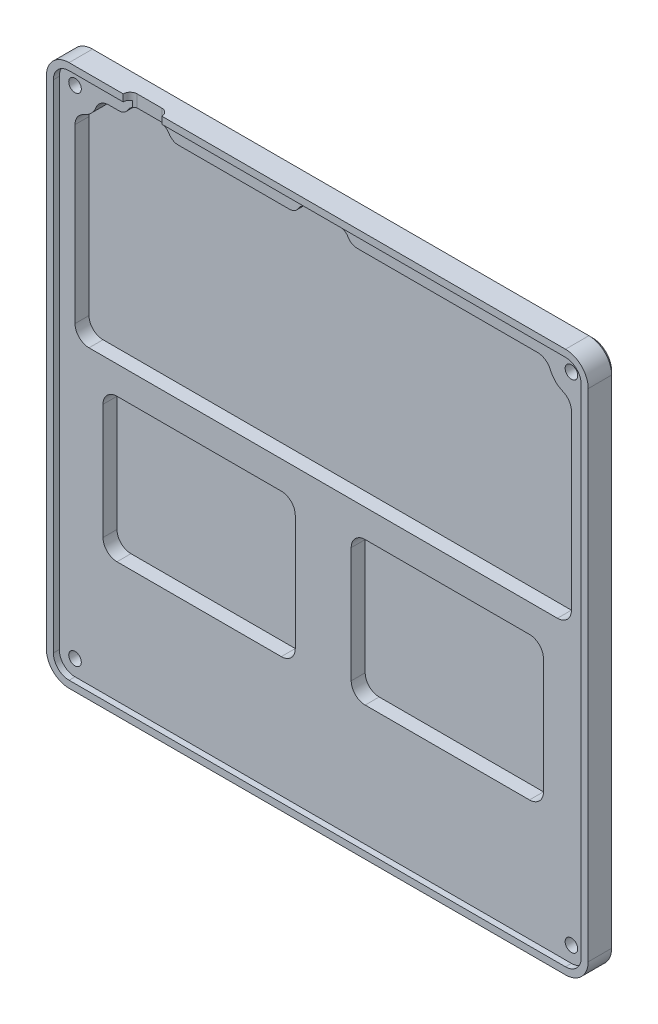
SolidWorks part; units mm, degrees
ref_plane "Front Plane" through (0, 0, 0) normal (0, 0, 1) x (1, 0, 0)
ref_plane "Top Plane" through (0, 0, 0) normal (0, 1, 0) x (1, 0, 0)
ref_plane "Right Plane" through (0, 0, 0) normal (1, 0, 0) x (0, 0, -1)
sketch "Sketch2" plane through (0, 0, 21.1137) normal (0, 0, -1) x (-1, 0, 0)
  line L0 (-26.4015, -76.7464) -> (-26.4015, 65.2536)
  line L1 (-25.9015, -80.7464) -> (124.0985, -80.7464) construction
  line L2 (-25.9015, -80.7464) -> (-25.9015, 69.2536) construction
  line L3 (-25.9015, 69.2536) -> (124.0985, 69.2536) construction
  line L4 (124.0985, -80.7464) -> (124.0985, 69.2536) construction
  line L5 (-21.9015, 69.7536) -> (120.0985, 69.7536)
  line L6 (124.5985, -76.7464) -> (124.5985, 65.2536)
  line L7 (-21.9015, -81.2464) -> (120.0985, -81.2464)
  line L8 (-28.4015, -76.7464) -> (-28.4015, 65.2536)
  line L9 (-21.9015, 71.7536) -> (120.0985, 71.7536)
  line L10 (126.5985, -76.7464) -> (126.5985, 65.2536)
  line L11 (-21.9015, -83.2464) -> (120.0985, -83.2464)
  line L15 (-26.4015, -81.2464) -> (-26.4015, 69.7536) construction
  line L16 (-26.4015, -81.2464) -> (124.5985, -81.2464) construction
  line L17 (-26.4015, 69.7536) -> (124.5985, 69.7536) construction
  line L18 (124.5985, -81.2464) -> (124.5985, 69.7536) construction
  line L19 (-28.4015, 71.7536) -> (126.5985, 71.7536) construction
  line L20 (126.5985, -83.2464) -> (126.5985, 71.7536) construction
  line L21 (-28.4015, -83.2464) -> (126.5985, -83.2464) construction
  line L22 (-28.4015, -83.2464) -> (-28.4015, 71.7536) construction
  line L23 (-21.9015, -80.7464) -> (120.0985, -80.7464) construction
  line L24 (124.0985, -76.7464) -> (124.0985, 65.2536) construction
  line L25 (120.0985, 69.2536) -> (-21.9015, 69.2536) construction
  arc A0 (-26.4015, -76.7464) -> (-21.9015, -81.2464) centre (-21.9015, -76.7464) ccw
  arc A1 (-26.4015, 65.2536) -> (-21.9015, 69.7536) centre (-21.9015, 65.2536) cw
  arc A2 (120.0985, 69.7536) -> (124.5985, 65.2536) centre (120.0985, 65.2536) cw
  arc A3 (124.5985, -76.7464) -> (120.0985, -81.2464) centre (120.0985, -76.7464) cw
  arc A4 (120.0985, 71.7536) -> (126.5985, 65.2536) centre (120.0985, 65.2536) cw
  arc A5 (126.5985, -76.7464) -> (120.0985, -83.2464) centre (120.0985, -76.7464) cw
  arc A6 (-28.4015, -76.7464) -> (-21.9015, -83.2464) centre (-21.9015, -76.7464) ccw
  arc A7 (-28.4015, 65.2536) -> (-21.9015, 71.7536) centre (-21.9015, 65.2536) cw
  dimension "D3" = 4.5
  dimension "D4" = 4.5
  dimension "D5" = 6.5
  dimension "D1" = 0.5
  dimension "D2" = 2
extrude "Boss-Extrude1" add sketch "Sketch2" against normal blind 1.7
sketch "Sketch4" plane through (0, 0, 21.1137) normal (0, 0, -1) x (-1, 0, 0)
  line L0 (-15.4015, 65.2536) -> (41.5985, 65.2536)
  line L4 (-28.4015, -76.7464) -> (-28.4015, 65.2536)
  line L6 (112.0985, -46.7464) -> (112.0985, -5.7464)
  line L8 (126.5985, -76.7464) -> (126.5985, 65.2536)
  line L11 (-21.9015, -83.2464) -> (120.0985, -83.2464)
  line L15 (112.0985, -46.7464) -> (57.0985, -46.7464)
  line L20 (41.0985, -46.7464) -> (41.0985, -5.7464)
  line L21 (120.0985, 2.2536) -> (-21.9015, 2.2536)
  line L23 (41.0985, -5.7464) -> (-13.9015, -5.7464)
  line L26 (41.5985, 68.2536) -> (56.5985, 68.2536)
  line L27 (56.5985, 68.2536) -> (56.5985, 65.2536)
  line L28 (56.5985, 65.2536) -> (92.7985, 65.2536)
  line L29 (92.7985, 65.2536) -> (92.7985, 68.2536)
  line L30 (92.7985, 68.2536) -> (105.3985, 68.2536)
  line L31 (105.3985, 68.2536) -> (105.3985, 65.2536)
  line L32 (105.3985, 65.2536) -> (113.5985, 65.2536)
  line L33 (120.0985, 71.7536) -> (-21.9015, 71.7536)
  line L34 (-13.9015, -46.7464) -> (-13.9015, -5.7464)
  line L35 (-15.4015, 65.2536) -> (41.5985, 65.2536) construction
  line L36 (-21.9015, 2.2536) -> (-21.9015, 58.7536)
  line L38 (41.5985, 65.2536) -> (41.5985, 68.2536)
  line L39 (120.0985, 69.7536) -> (-21.9015, 69.7536) construction
  line L40 (57.0985, -46.7464) -> (57.0985, -5.7464)
  line L41 (57.0985, -5.7464) -> (112.0985, -5.7464)
  line L45 (41.0985, -46.7464) -> (-13.9015, -46.7464)
  line L46 (120.0985, 2.2536) -> (120.0985, 58.7536)
  line L47 (41.0985, -5.7464) -> (57.0985, -5.7464) construction
  line L48 (-13.9015, -46.7464) -> (-28.4015, -46.7464) construction
  line L49 (112.0985, -46.7464) -> (126.5985, -46.7464) construction
  arc A0 (-21.9015, 71.7536) -> (-28.4015, 65.2536) centre (-21.9015, 65.2536) ccw
  arc A2 (-21.9015, 71.7536) -> (-28.4015, 65.2536) centre (-21.9015, 65.2536) ccw construction
  arc A3 (-28.4015, -76.7464) -> (-21.9015, -83.2464) centre (-21.9015, -76.7464) ccw
  arc A4 (120.0985, -83.2464) -> (126.5985, -76.7464) centre (120.0985, -76.7464) ccw
  arc A5 (126.5985, 65.2536) -> (120.0985, 71.7536) centre (120.0985, 65.2536) ccw
  arc A6 (126.5985, 65.2536) -> (120.0985, 71.7536) centre (120.0985, 65.2536) ccw construction
  arc A7 (120.0985, -83.2464) -> (126.5985, -76.7464) centre (120.0985, -76.7464) ccw construction
  arc A8 (-28.4015, -76.7464) -> (-21.9015, -83.2464) centre (-21.9015, -76.7464) ccw construction
  arc A11 (-21.9015, 58.7536) -> (-15.4015, 65.2536) centre (-21.9015, 65.2536) ccw
  arc A12 (126.5985, 65.2536) -> (120.0985, 71.7536) centre (120.0985, 65.2536) ccw
  arc A13 (113.5985, 65.2536) -> (120.0985, 58.7536) centre (120.0985, 65.2536) ccw
  arc A14 (103.3485, 64.6286) -> (102.4485, 64.6286) centre (102.8985, 64.6286) ccw construction
  arc A15 (95.7485, 64.6286) -> (94.8485, 64.6286) centre (95.2985, 64.6286) ccw construction
  point P19 (84.5985, -5.7464)
  line M1 (120.0985, -81.2464) -> (-21.9015, -81.2464)
  arc M2 (-21.9015, -81.2464) -> (-26.4015, -76.7464) centre (-21.9015, -76.7464) cw
  line M3 (-26.4015, -76.7464) -> (-26.4015, 65.2536)
  arc M4 (-26.4015, 65.2536) -> (-21.9015, 69.7536) centre (-21.9015, 65.2536) cw
  line M5 (-21.9015, 69.7536) -> (120.0985, 69.7536)
  arc M6 (120.0985, 69.7536) -> (124.5985, 65.2536) centre (120.0985, 65.2536) cw
  line M7 (124.5985, 65.2536) -> (124.5985, -76.7464)
  arc M8 (124.5985, -76.7464) -> (120.0985, -81.2464) centre (120.0985, -76.7464) cw
  arc M9 (126.5985, 65.2536) -> (120.0985, 71.7536) centre (120.0985, 65.2536) ccw
  line M10 (120.0985, 71.7536) -> (-21.9015, 71.7536)
  arc M11 (-21.9015, 71.7536) -> (-28.4015, 65.2536) centre (-21.9015, 65.2536) ccw
  line M12 (-28.4015, 65.2536) -> (-28.4015, -76.7464)
  arc M13 (-28.4015, -76.7464) -> (-21.9015, -83.2464) centre (-21.9015, -76.7464) ccw
  line M14 (-21.9015, -83.2464) -> (120.0985, -83.2464)
  arc M15 (120.0985, -83.2464) -> (126.5985, -76.7464) centre (120.0985, -76.7464) ccw
  line M16 (126.5985, -76.7464) -> (126.5985, 65.2536)
  dimension "D7" = 2.5
  dimension "D8" = 2.5
  dimension "D1" = 55
  dimension "D2" = 16
  dimension "D3" = 8
  dimension "D4" = 8
  dimension "D5" = 1.5
  dimension "D6" = 6.5
  dimension "D9" = 6.5
  dimension "D10" = 56.5
  dimension "D11" = 41
  dimension "D12" = 70
  dimension "D13" = 70
extrude "Boss-Extrude2" add sketch "Sketch4" along normal blind 4 contours M16 M9 M10 M11 M12 M13 M14 M15 M8 M1 M2 M3 M4 M5 M6 M7 | L40 L41 L6 L15 L20 L45 L34 L23 L32 A13 L46 L21 L36 A11 L0 L38 L26 L27 L28 L29 L30 L31 M1 M8 M7 M6 M5 M4 M3 M2 region at (28.1823, -5.7464, 21.1137) region at (-48.8955, -33.926, 21.1137)
fillet "Fillet1" radius 4 14 edges at (-112.0985, -46.7464, 19.1137) (-112.0985, -5.7464, 19.1137) (-57.0985, -5.7464, 19.1137) (-57.0985, -46.7464, 19.1137) (-41.0985, -46.7464, 19.1137) (13.9015, -46.7464, 19.1137) (13.9015, -5.7464, 19.1137) (-41.0985, -5.7464, 19.1137) (21.9015, 58.7536, 19.1137) (15.4015, 65.2536, 19.1137) (-120.0985, 2.2536, 19.1137) (21.9015, 2.2536, 19.1137) (-120.0985, 58.7536, 19.1137) (-113.5985, 65.2536, 19.1137)
fillet "Fillet2" radius 3 4 edges at (-92.7985, 68.2536, 19.1137) (-105.3985, 68.2536, 19.1137) (-41.5985, 68.2536, 19.1137) (-56.5985, 68.2536, 19.1137)
fillet "Fillet3" radius 3 4 edges at (-41.5985, 65.2536, 19.1137) (-56.5985, 65.2536, 19.1137) (-105.3985, 65.2536, 19.1137) (-92.7985, 65.2536, 19.1137)
sketch "Sketch8" plane through (0, 0, 17.1137) normal (0, 0, -1) x (-1, 0, 0)
  line L8 (-21.9015, -83.2464) -> (120.0985, -83.2464) construction
  line L9 (126.5985, -76.7464) -> (126.5985, 65.2536) construction
  line L10 (120.0985, 71.7536) -> (-21.9015, 71.7536) construction
  line L11 (-28.4015, 65.2536) -> (-28.4015, -76.7464) construction
  line L12 (-21.9015, -83.2464) -> (120.0985, -83.2464)
  line L13 (126.5985, -76.7464) -> (126.5985, 65.2536)
  line L14 (120.0985, 71.7536) -> (-21.9015, 71.7536)
  line L15 (-28.4015, 65.2536) -> (-28.4015, -76.7464)
  arc A8 (-28.4015, -76.7464) -> (-21.9015, -83.2464) centre (-21.9015, -76.7464) ccw construction
  arc A9 (120.0985, -83.2464) -> (126.5985, -76.7464) centre (120.0985, -76.7464) ccw construction
  arc A10 (126.5985, 65.2536) -> (120.0985, 71.7536) centre (120.0985, 65.2536) ccw construction
  arc A11 (-21.9015, 71.7536) -> (-28.4015, 65.2536) centre (-21.9015, 65.2536) ccw construction
  arc A12 (-28.4015, -76.7464) -> (-21.9015, -83.2464) centre (-21.9015, -76.7464) ccw
  arc A13 (120.0985, -83.2464) -> (126.5985, -76.7464) centre (120.0985, -76.7464) ccw
  arc A14 (126.5985, 65.2536) -> (120.0985, 71.7536) centre (120.0985, 65.2536) ccw
  arc A15 (-21.9015, 71.7536) -> (-28.4015, 65.2536) centre (-21.9015, 65.2536) ccw
extrude "Boss-Extrude3" add sketch "Sketch8" along normal blind 2
sketch "Sketch9" plane through (0, 71.7536, 0) normal (0, 1, 0) x (1, 0, 0)
  circle A0 centre (-99.0985, -26.3795) radius 5.525
  arc A3 (-94.2735, -26.3795) -> (-103.9235, -26.3795) centre (-99.0985, -26.3795) ccw construction
  arc A4 (-101.4085, -26.3795) -> (-96.7885, -26.3795) centre (-99.0985, -26.3795) ccw construction
  dimension "D1" = 0.7
extrude "Cut-Extrude1" cut sketch "Sketch9" against normal up to surface (3.5 mm away) up to face at (-99.0985, 68.2536, 19.1137)
chamfer "Chamfer1" distance 1 angle 45 8 edges at (28.4015, -5.7464, 15.1137) (26.4977, 69.8498, 15.1137) (-49.0985, 71.7536, 15.1137) (-124.6947, 69.8498, 15.1137) (-126.5985, -5.7464, 15.1137) (-124.6947, -81.3426, 15.1137) (-49.0985, -83.2464, 15.1137) (26.4977, -81.3426, 15.1137)
hole_wizard "CSK for M3 Flat Head Machine Screw2" positions "Sketch14" profile "Sketch13" countersink size "M3" standard "ANSI Metric" end condition through all
sketch "Sketch14" plane through (0, 0, 15.1137) normal (0, 0, -1) x (-1, 0, 0)
  point P0 (-21.9015, 65.2536)
  point P3 (120.0985, 65.2536)
  point P6 (120.0985, -76.7464)
  point P9 (-21.9015, -76.7464)
sketch "Sketch13" plane through (21.9015, 65.2536, 15.1137) normal (1, 0, 0) x (0, 1, 0)
  line L0 (0, 0) -> (0, 7.7)
  line L1 (0, 7.7) -> (1.8, 7.7)
  line L2 (1.8, 7.7) -> (1.8, 1.55)
  line L3 (1.8, 1.55) -> (3.35, 0)
  line L5 (3.35, 0) -> (0, 0)
  line L6 (-1.8, 1.55) -> (-3.35, 0) construction
  line L11 (0, -6.35) -> (0, 107.95) construction
  dimension "Thru Hole Dia." = 3.6
  dimension "Thru Hole Depth" = 7.7
  dimension "Near C'Sink Dia." = 6.7
  dimension "Near C'Sink Angle" = 90
sketch "Sketch15" plane through (0, 71.7536, 0) normal (0, 1, 0) x (1, 0, 0)
  line L0 (-120.0985, -22.8137) -> (-103.3188, -22.8137) construction
  line L1 (-104.6235, -22.8137) -> (-93.5735, -22.8137)
  line L2 (-104.6235, -22.8137) -> (-104.6235, -20.8137)
  line L3 (-104.6235, -20.8137) -> (-93.5735, -20.8137)
  line L4 (-93.5735, -22.8137) -> (-93.5735, -20.8137)
  line L5 (-104.6235, -22.8137) -> (-104.6235, -26.3795) construction
  line L6 (-94.8782, -22.8137) -> (21.9015, -22.8137) construction
  line L7 (-93.5735, -26.3795) -> (-93.5735, -22.8137) construction
  point P8 (-93.3754, -22.8137)
  dimension "D1" = 2
extrude "Cut-Extrude2" cut sketch "Sketch15" against normal up to next
fillet "Fillet4" radius 2 2 edges at (-93.5735, 69.5098, 20.8137) (-104.6235, 69.5098, 20.8137)
